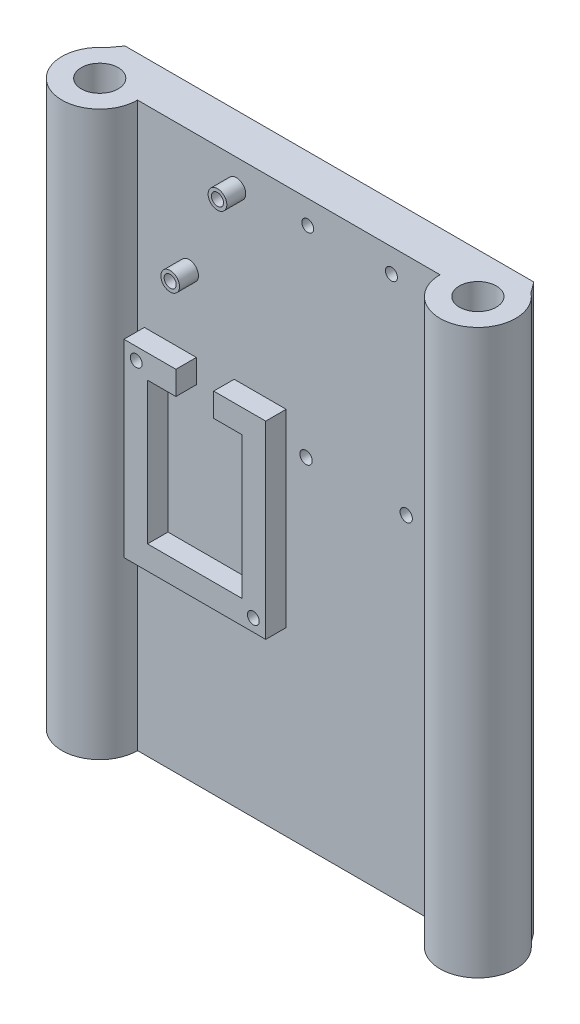
SolidWorks part; units mm, degrees
material "ABS"
ref_plane "Front Plane" through (0, 0, 0) normal (0, 0, 1) x (1, 0, 0)
ref_plane "Top Plane" through (0, 0, 0) normal (0, 1, 0) x (1, 0, 0)
ref_plane "Right Plane" through (0, 0, 0) normal (1, 0, 0) x (0, 0, -1)
sketch "Sketch1" plane through (0, 0, 0) normal (0, 1, 0) x (1, 0, 0)
  line L0 (-50.8, 0) -> (50.8, 0) construction
  line L1 (-40.64, 0) -> (40.64, 0)
  line L2 (-54.8982, 10.9145) -> (54.8982, 10.9145)
  circle A0 centre (-50.8, 0) radius 4.9609
  circle A1 centre (50.8, 0) radius 4.9609
  circle A2 centre (-50.8, 0) radius 10.16
  circle A4 centre (50.8, 0) radius 10.16
  arc A5 (57.0241, 8.0303) -> (-57.0241, 8.0303) centre (0, -31.7761) ccw
  point P4 (0, 0)
  dimension "D1" = 9.9219
  dimension "D2" = 101.6
  dimension "D3" = 20.32
extrude "Boss-Extrude1" add sketch "Sketch1" along normal mid plane 151.384 contours A0 A2 | A4 A1 | A4 A5 L2 A2 L1 region at (0, 0, -5.7083) region at (-55.145, 0, 8.8651) region at (46.455, 0, -8.8651)
sketch "Sketch2" plane through (0, 0, 0) normal (0, 0, 1) x (1, 0, 0)
  line L0 (-23.2789, 0) -> (23.2789, 0) construction
  line L1 (-23.2789, -45.2995) -> (23.2789, -45.2995) construction
  line L2 (-23.2789, -45.2995) -> (-23.2789, 45.2995) construction
  line L3 (-23.2789, 45.2995) -> (23.2789, 45.2995) construction
  line L4 (23.2789, -45.2995) -> (23.2789, 45.2995) construction
  line L5 (-23.2789, -45.2995) -> (23.2789, 45.2995) construction
  line L6 (-23.2789, 45.2995) -> (23.2789, -45.2995) construction
  circle A0 centre (-23.2789, 45.2995) radius 3.175
  circle A1 centre (23.2789, 45.2995) radius 3.175
  circle A2 centre (23.2789, -45.2995) radius 3.175
  circle A3 centre (-23.2789, -45.2995) radius 3.175
  point P0 (0, 0)
  dimension "D1" = 6.35
sketch "Sketch3" plane through (0, 0, 0) normal (0, 0, 1) x (1, 0, 0)
  circle A0 centre (-14.0871, 68.405) radius 1.6256
  circle A1 centre (-26.7871, 43.005) radius 1.6256
  circle A2 centre (-14.0871, 68.405) radius 2.5114
  circle A3 centre (-26.7871, 43.005) radius 2.5114
  point P6 (0, 0)
  point P7 (0, 0)
  dimension "D1" = 3.2512
  dimension "D2" = 12.7
  dimension "D3" = 25.4
extrude "Cut-Extrude1" cut sketch "Sketch3" against normal through all contours A0 | A1
extrude "Boss-Extrude2" add sketch "Sketch3<3>" along normal blind 5.08
sketch "Sketch3<3>" plane through (0, 0, 0) normal (0, 0, 1) x (1, 0, 0) same geometry as "Sketch3"
sketch "Sketch4" plane through (0, 0, 0) normal (0, 0, 1) x (1, 0, 0)
  circle A0 centre (5.0971, 69.338) radius 1.5806
  circle A1 centre (27.5695, 69.3267) radius 1.616
  circle A3 centre (4.6303, 15.1788) radius 1.651
  circle A4 centre (31.5543, 15.1951) radius 1.651
extrude "Cut-Extrude2" cut sketch "Sketch4" against normal through all
sketch "Sketch5" plane through (0, 0, 0) normal (0, 0, 1) x (1, 0, 0)
  line L0 (-24.8378, 17.3607) -> (-24.8378, 23.7107)
  line L1 (-32.4578, -20.7393) -> (-7.0578, -20.7393)
  line L2 (-32.4578, -20.7393) -> (-32.4578, 17.3607)
  line L3 (-32.4578, 17.3607) -> (-7.0578, 17.3607)
  line L4 (-7.0578, -20.7393) -> (-7.0578, 17.3607)
  line L5 (-32.4578, -20.7393) -> (-7.0578, 17.3607) construction
  line L6 (-32.4578, 17.3607) -> (-7.0578, -20.7393) construction
  line L7 (-0.7078, -27.0893) -> (-38.8078, -27.0893)
  line L8 (-0.7078, -27.0893) -> (-0.7078, 23.7107)
  line L9 (-0.7078, 23.7107) -> (-38.8078, 23.7107)
  line L10 (-38.8078, -27.0893) -> (-38.8078, 23.7107)
  line L11 (-0.7078, -27.0893) -> (-38.8078, 23.7107) construction
  line L12 (-0.7078, 23.7107) -> (-38.8078, -27.0893) construction
  line L13 (-14.6778, 17.3607) -> (-14.6778, 23.7107)
  point P0 (-19.7578, -1.6893)
  point P6 (-19.7578, -1.6893)
  point P14 (-19.7578, 17.3607)
  dimension "D1" = 25.4
  dimension "D2" = 38.1
  dimension "D3" = 50.8
  dimension "D4" = 5.08
  dimension "D5" = 5.08
  dimension "D6" = 38.1
extrude "Boss-Extrude3" add sketch "Sketch5" along normal blind 5.5001 contours L13 L3 L4 L1 L2 L0 L9 L10 L7 L8 region at (-28.6478, 17.9957, 0)
sketch "Sketch6" plane through (0, 0, 5.5001) normal (0, 0, 1) x (1, 0, 0)
  line L0 (-35.4829, 23.7107) -> (-35.4829, 20.3858) construction
  line L1 (-24.8378, 23.7107) -> (-38.8078, 23.7107) construction
  line L2 (-38.8078, 20.3858) -> (-35.4829, 20.3858) construction
  line L3 (-38.8078, -27.0893) -> (-38.8078, 23.7107) construction
  line L4 (-0.7078, -23.7644) -> (-4.0327, -23.7644) construction
  line L5 (-0.7078, -27.0893) -> (-0.7078, 23.7107) construction
  line L6 (-4.0327, -23.7644) -> (-4.0327, -27.0893) construction
  line L7 (-0.7078, -27.0893) -> (-38.8078, -27.0893) construction
  circle A0 centre (-35.4829, 20.3858) radius 1.5875
  circle A1 centre (-4.0327, -23.7644) radius 1.5875
  dimension "D1" = 3.175
  dimension "D2" = 3.175
extrude "Cut-Extrude3" cut sketch "Sketch6" against normal through all
